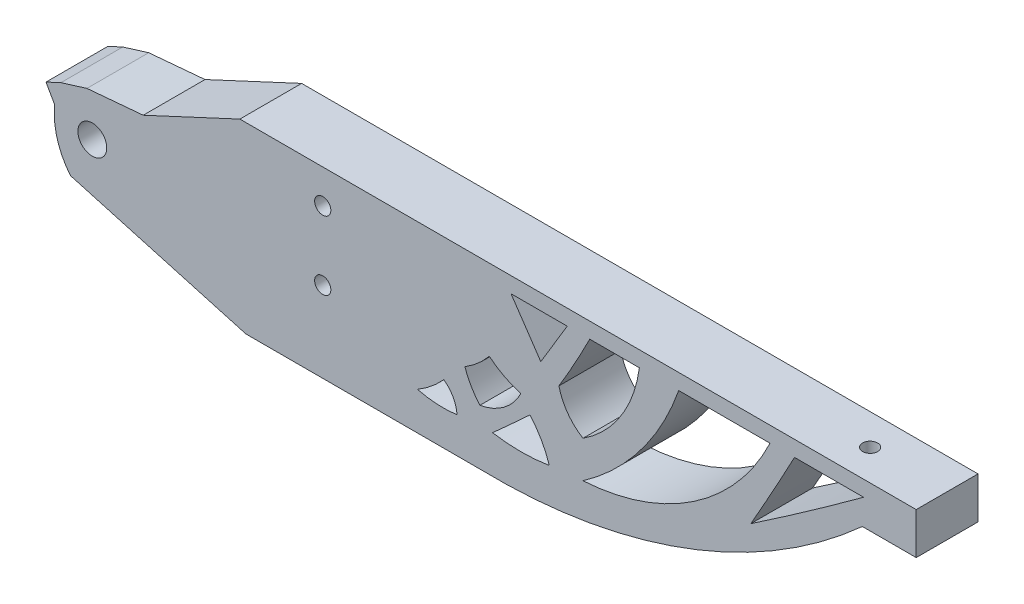
SolidWorks part; units mm, degrees
ref_plane "Front Plane" through (0, 0, 0) normal (0, 0, 1) x (1, 0, 0)
ref_plane "Top Plane" through (0, 0, 0) normal (0, 1, 0) x (1, 0, 0)
ref_plane "Right Plane" through (0, 0, 0) normal (1, 0, 0) x (0, 0, -1)
sketch "Sketch1" plane through (0, 0, 0) normal (0, 0, 1) x (1, 0, 0)
  line L1 (120.65, 25.4) -> (-120.65, 25.4)
  line L2 (120.65, 25.4) -> (120.65, -25.4)
  line L3 (120.65, -25.4) -> (-120.65, -25.4)
  line L4 (-120.65, 25.4) -> (-120.65, -25.4)
  line L5 (120.65, 25.4) -> (-120.65, -25.4) construction
  line L6 (120.65, -25.4) -> (-120.65, 25.4) construction
  point P0 (0, 0)
  dimension "D1" = 241.3
  dimension "D2" = 50.8
extrude "Boss-Extrude1" add sketch "Sketch1" along normal blind 17.145
sketch "Sketch3" plane through (0, 0, 17.145) normal (0, 0, 1) x (1, 0, 0)
  line L0 (0, 0) -> (-120.65, 0) construction
  line L1 (-120.65, 25.4) -> (-120.65, -25.4) construction
  circle A0 centre (-107.95, 0) radius 4
  dimension "D2" = 8
  dimension "D1" = 12.7
extrude "Cut-Extrude1" cut sketch "Sketch3" against normal through all
sketch "Sketch5" plane through (0, 0, 17.145) normal (0, 0, 1) x (1, 0, 0)
  line L0 (-120.65, -25.4) -> (120.65, -25.4) construction
  line L1 (-111.232, -5.4361) -> (-109.6883, -6.1074)
  line L2 (-107.95, 6.35) -> (-67.0151, 25.4)
  line L3 (120.65, 25.4) -> (-120.65, 25.4) construction
  line L4 (-67.0151, 25.4) -> (-120.65, 25.4)
  line L5 (-120.65, 25.4) -> (-120.65, -25.4)
  line L6 (-120.65, -25.4) -> (-65.3282, -25.4)
  line L7 (120.65, 13.8537) -> (120.65, -25.4)
  line L8 (120.65, -25.4) -> (0, -25.4)
  line L9 (120.65, 13.8537) -> (105.7036, 13.8537)
  line L13 (-112.2793, 4.6454) -> (-116.6487, 9.3339)
  line L14 (-114.0227, -11.694) -> (-65.3282, -25.4)
  arc A0 (0, -25.4) -> (105.7036, 13.8537) centre (3.5611, 126.9584) ccw
  arc A1 (-109.9582, -6.0241) -> (-114.0227, -1.8561) centre (-107.95, 0) ccw construction
  arc A2 (-107.95, 6.35) -> (-112.2793, 4.6454) centre (-107.95, 0) ccw
  arc A5 (-116.6487, 9.3339) -> (-114.0227, -11.694) centre (-98.496, 0.9229) ccw
  point P15 (-116.1445, -2.9908)
  line M3 (-120.65, 25.4) -> (-120.65, -25.4)
  line M4 (-120.65, -25.4) -> (120.65, -25.4)
  line M5 (120.65, -25.4) -> (120.65, 25.4)
  line M6 (120.65, 25.4) -> (-120.65, 25.4)
  dimension "D1" = 152.4
  dimension "D2" = 12.7
  dimension "D3" = 45.1505
  dimension "D4" = 45.9039
extrude "Cut-Extrude2" cut sketch "Sketch5" against normal through all contours A2 L2 L1 M6 M3 M4 | A0 L8 M5 region at (-110.5515, 6.6074, 17.145) region at (91.2141, -11.3337, 17.145)
sketch "Sketch6" plane through (0, 0, 17.145) normal (0, 0, 1) x (1, 0, 0)
  line L0 (-107.95, 0) -> (87.8661, 0) construction
  arc A0 (7.1222, -25.4) -> (105.7036, 13.8537) centre (3.5611, 126.9584) ccw construction
  circle A1 centre (19.05, 0) radius 3.1347
  dimension "D1" = 127
sketch "Sketch7" plane through (0, 0, 0) normal (0, 0, -1) x (-1, 0, 0)
  line L0 (44.0204, -2.9977) -> (44.0204, 16.0523) construction
  point P3 (44.0204, -2.9977)
  point P4 (44.0204, 16.0523)
  dimension "D1" = 19.05
sketch "Sketch8" plane through (0, 0, 0) normal (0, 0, -1) x (-1, 0, 0)
  point P0 (44.0204, 16.0523)
  point P3 (44.0204, -2.9977)
hole_wizard "#8 Clearance Hole1" positions "Sketch8" profile "Sketch9" hole size "#8" standard "ANSI Inch" end condition through all
sketch "Sketch9" plane through (-44.0204, 16.0523, 0) normal (1, 0, 0) x (0, 1, 0)
  line L0 (0, 0) -> (0, 17.145)
  line L1 (0, 17.145) -> (2.2479, 17.145)
  line L2 (2.2479, 17.145) -> (2.2479, 0)
  line L5 (2.2479, 0) -> (0, 0)
  line L11 (0, -6.35) -> (0, 107.95) construction
  dimension "Thru Hole Dia." = 4.4958
  dimension "Thru Hole Depth" = 17.145
ref_plane "Plane1" through (-114.3, 0, 0) normal (-1, 0, 0) x (0, 0, 1)
sketch "Sketch10" plane through (-114.3, 0, 0) normal (-1, 0, 0) x (0, 0, 1)
  line L0 (0, 0) -> (17.145, 0) construction
  line L1 (17.145, -3.1347) -> (17.145, 3.1347) construction
  circle A0 centre (6.0894, 0) radius 1.905
  dimension "D1" = 3.81
sketch "Sketch11" plane through (0, 0, 17.145) normal (0, 0, 1) x (1, 0, 0)
  line L0 (-93.8249, 12.9234) -> (-109.4459, 12.9234) construction
  line L1 (-107.95, 6.35) -> (-67.0151, 25.4) construction
  line L2 (-109.4459, 12.9234) -> (-109.4459, 11.5568) construction
  line L3 (-93.8249, 12.9234) -> (-109.4459, 5.6538)
  line L4 (-93.8249, 12.9234) -> (-109.4459, 11.5568)
  line L6 (-116.6487, 9.3339) -> (-109.4459, 11.5568)
  line L7 (-116.6487, 9.3339) -> (-120.8046, 7.3998)
  line L10 (-118.3814, 3.1212) -> (-116.993, 0.7917)
  line L11 (-116.993, 0.7917) -> (-109.4459, 5.6538)
  line L12 (-120.8046, 7.3998) -> (-118.3814, 3.1212)
  arc A0 (-116.6487, 9.3339) -> (-114.0227, -11.694) centre (-98.496, 0.9229) ccw construction
  circle A1 centre (-107.95, 0) radius 4 construction
  dimension "D2" = 5.6538
  dimension "D3" = 175
extrude "Boss-Extrude2" add sketch "Sketch11" against normal up to surface (17.145 mm away) up to face at (-46.2683, 16.0523, 0)
sketch "Sketch18" plane through (0, 25.4, 0) normal (0, 1, 0) x (1, 0, 0)
  circle A0 centre (99.2867, -8.5725) radius 2.0828
extrude "Cut-Extrude9" cut sketch "Sketch18" against normal through all contours A0
sketch "Sketch19" plane through (0, 0, 17.145) normal (0, 0, 1) x (1, 0, 0)
  line L3 (86.8867, 21.0579) -> (106.0483, 21.0579)
  line L4 (54.7502, 21.0579) -> (80.0838, 21.0579)
  line L5 (43.8283, 21.0579) -> (30.0654, 21.0579)
  line L6 (21.5195, 21.0579) -> (8.2267, 21.0579)
  line L7 (8.2267, 21.0579) -> (16.4852, 8.8568)
  line L8 (16.4852, 8.8568) -> (23.8201, 21.0579)
  line L9 (23.8201, 21.0579) -> (21.5195, 21.0579)
  arc A0 (106.0483, 21.0579) -> (74.7548, -0.9382) centre (-476.4178, 816.4626) cw
  arc A1 (86.8867, 21.0579) -> (74.7548, -0.9382) centre (-617.5859, 395.2635) cw
  arc A2 (80.0838, 21.0579) -> (28.1833, -13.9058) centre (24.5582, 47.4779) cw
  arc A3 (28.1833, -13.9058) -> (54.7502, 21.0579) centre (-12.7332, 44.7595) ccw
  arc A4 (30.0654, 21.0579) -> (21.5195, 5.5624) centre (-173.1779, 123.0437) cw
  arc A5 (43.8283, 21.0579) -> (28.1833, -3.6987) centre (9.3178, 25.5453) cw
  arc A6 (28.1833, -3.6987) -> (21.5195, 5.5624) centre (35.8652, 8.8568) cw
  arc A7 (3.09, -14.9046) -> (13.4624, -5.4583) centre (-508.9074, 557.7064) ccw
  arc A8 (13.4624, -5.4583) -> (18.8338, -14.9046) centre (-5.5007, -22.4915) cw
  arc A9 (18.8338, -14.9046) -> (3.09, -14.9046) centre (10.9619, 32.5583) cw
  arc A10 (2.2235, 3.0165) -> (-4.5776, -2.8864) centre (-19.0872, 20.7005) cw
  arc A11 (2.2235, 3.0165) -> (10.9619, -1.539) centre (16.8059, 20.3296) ccw
  arc A12 (10.9619, -1.539) -> (-0.4071, -10.0726) centre (-3.0644, 5.3078) cw
  arc A13 (-4.5776, -2.8864) -> (-0.4071, -10.0726) centre (15.1613, 3.7659) ccw
  arc A14 (-10.4164, -8.9177) -> (-6.7592, -15.5263) centre (-15.593, -16.0987) cw
  arc A15 (-6.7592, -15.5263) -> (-17.7308, -14.9046) centre (-10.6309, 13.2663) cw
  arc A16 (-17.7308, -14.9046) -> (-10.4164, -8.9177) centre (-33.6495, 12.0056) ccw
extrude "Cut-Extrude10" cut sketch "Sketch19" against normal through all
